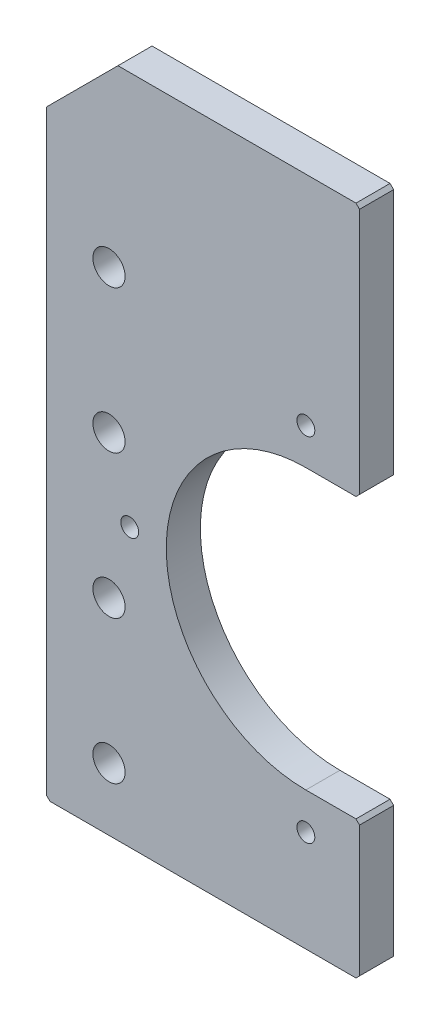
SolidWorks part; units mm, degrees
material "6061-T6 (SS)"
ref_plane "Front Plane" through (0, 0, 0) normal (0, 0, 1) x (1, 0, 0)
ref_plane "Top Plane" through (0, 0, 0) normal (0, 1, 0) x (1, 0, 0)
ref_plane "Right Plane" through (0, 0, 0) normal (1, 0, 0) x (0, 0, -1)
sketch "Sketch1" plane through (0, 0, 0) normal (0, 0, 1) x (1, 0, 0)
  line L0 (0, -39) -> (15, -39)
  line L1 (15, -39) -> (15, -77.5)
  line L2 (15, -77.5) -> (-72.5, -77.5)
  line L3 (-72.5, -77.5) -> (-72.5, 90)
  line L4 (-72.5, 90) -> (-52.5, 110)
  line L5 (-52.5, 110) -> (15, 110)
  line L6 (15, 110) -> (15, 39)
  line L7 (15, 39) -> (0, 39)
  line L8 (-35, 8.8681) -> (-35, 0) construction
  line L9 (-25, 15.1907) -> (-25, 3.6129) construction
  line L10 (-55, 60) -> (-55, 20) construction
  line L11 (-55, 20) -> (-55, -20) construction
  line L12 (-55, -20) -> (-55, -60) construction
  line L13 (55, 0) -> (-55, 0) construction
  arc A0 (0, 39) -> (0, -39) centre (0, 0) ccw
  circle A1 centre (0, 0) radius 49.2125 construction
  point P19 (0, 49.2125)
  point P20 (-49.2125, 0)
  point P21 (0, -49.2125)
  point P22 (-55, 0)
  dimension "D12" = 98.425
  dimension "D1" = 10
  dimension "D2" = 25
  dimension "D3" = 17.5
  dimension "D4" = 40
  dimension "D5" = 20
  dimension "D6" = 17.5
  dimension "D7" = 110
  dimension "D8" = 78
  dimension "D9" = 45
  dimension "D10" = 50
  dimension "D11" = 90
extrude "Boss-Extrude1" add sketch "Sketch1" along normal mid plane 9.525
hole_wizard "M8 Clearance Hole1" positions "Sketch2" profile "Sketch3" hole size "M8" standard "ANSI Metric" end condition up to next
sketch "Sketch2" plane through (0, 0, 4.7625) normal (0, 0, 1) x (1, 0, 0)
  point P0 (-55, 60)
  point P3 (-55, 20)
  point P6 (-55, -20)
  point P9 (-55, -60)
sketch "Sketch3" plane through (-55, 60, 4.7625) normal (1, 0, 0) x (0, -1, 0)
  line L0 (0, 0) -> (0, 9.525)
  line L1 (0, 9.525) -> (4.5, 9.525)
  line L2 (4.5, 9.525) -> (4.5, 0)
  line L5 (4.5, 0) -> (0, 0)
  line L11 (0, -6.35) -> (0, 107.95) construction
  dimension "Thru Hole Dia." = 9
  dimension "Thru Hole Depth" = 9.525
hole_wizard "M6x1.0 Tapped Hole1" positions "Sketch4" profile "Sketch5" tap size "M6x1.0" standard "ANSI Metric" end condition up to next
sketch "Sketch4" plane through (0, 0, 4.7625) normal (0, 0, 1) x (1, 0, 0)
  point P0 (0, 49.2125)
  point P3 (-49.2125, 0)
  point P6 (0, -49.2125)
sketch "Sketch5" plane through (0, 49.2125, 4.7625) normal (1, 0, 0) x (0, -1, 0)
  line L0 (0, 0) -> (0, 9.525)
  line L1 (0, 9.525) -> (2.5, 9.525)
  line L2 (2.5, 9.525) -> (2.5, 0)
  line L5 (2.5, 0) -> (0, 0)
  line L11 (0, -6.35) -> (0, 107.95) construction
  dimension "Thru Tap Drill Dia." = 5
  dimension "Thru Tap Drill Depth" = 9.525
cosmetic thread "Hole Thread1" parameters "D2"=6
cosmetic thread "Hole Thread2" parameters "D2"=6
cosmetic thread "Hole Thread3" parameters "D2"=6
chamfer "Chamfer1" distance 1 5 edges at (-72.5, -77.5, 0) (15, -77.5, 0) (15, -39, 0) (15, 39, 0) (15, 110, 0)
